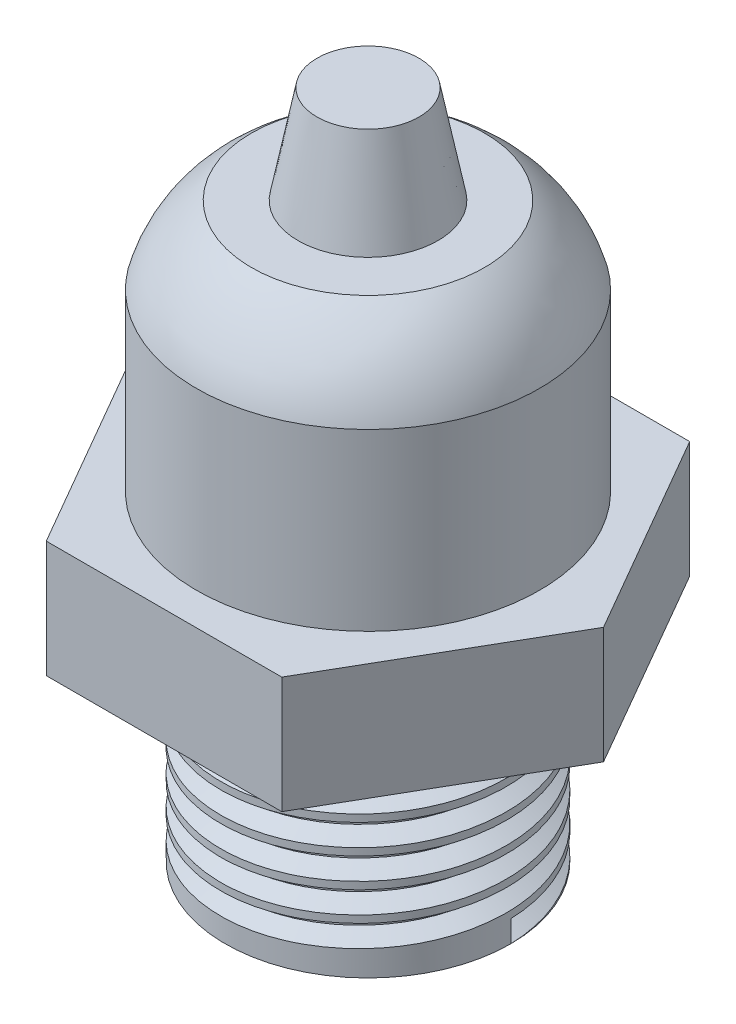
SolidWorks part; units mm, degrees
ref_plane "Front Plane" through (0, 0, 0) normal (0, 0, 1) x (1, 0, 0)
ref_plane "Top Plane" through (0, 0, 0) normal (0, 1, 0) x (1, 0, 0)
ref_plane "Right Plane" through (0, 0, 0) normal (1, 0, 0) x (0, 0, -1)
sketch "Sketch1" plane through (0, 0, 0) normal (0, 1, 0) x (1, 0, 0)
  line L1 (8.0829, 0) -> (4.0415, 7)
  line L2 (4.0415, 7) -> (-4.0415, 7)
  line L3 (-4.0415, 7) -> (-8.0829, 0)
  line L4 (-8.0829, 0) -> (-4.0415, -7)
  line L5 (-4.0415, -7) -> (4.0415, -7)
  line L6 (4.0415, -7) -> (8.0829, 0)
  circle A0 centre (0, 0) radius 7 construction
  dimension "D1" = 14
extrude "Boss-Extrude1" add sketch "Sketch1" along normal blind 4
sketch "Sketch3" plane through (0, 0, 0) normal (0, 0, 1) x (1, 0, 0)
  line L0 (0, 4) -> (0, 16) construction
  line L1 (-4.0415, 4) -> (4.0415, 4) construction
  line L2 (0, 16) -> (1.75, 16)
  line L3 (1.75, 16) -> (2.4, 12.65)
  line L4 (2.4, 12.65) -> (0, 12.65) construction
  line L5 (2.4, 12.65) -> (4, 12.65)
  line L6 (5.8875, 4) -> (5.8875, 10)
  line L7 (4.0415, 4) -> (8.0829, 4) construction
  line L8 (0, 16) -> (0, 4)
  line L9 (0, 4) -> (5.8875, 4)
  arc A0 (4, 12.65) -> (5.8875, 10) centre (1.3088, 8.7359) cw
  dimension "D8" = 4.75
  dimension "D1" = 12
  dimension "D2" = 1.75
  dimension "D3" = 3.35
  dimension "D4" = 2.4
  dimension "D5" = 4
  dimension "D6" = 5.8875
  dimension "D7" = 6
revolve "Revolve1" add sketch "Sketch3" angle 360 about L8 region at (2.6283, 8.9395, 0)
sketch "Sketch4" plane through (0, 0, 0) normal (0, -1, 0) x (1, 0, 0)
  line L0 (3.55, 0) -> (4.9, 0) construction
  circle A0 centre (0, 0) radius 4.9
  circle A1 centre (0, 0) radius 3.55
  point P6 (0, 0)
  dimension "D2" = 9.8
  dimension "D1" = 1.35
extrude "Boss-Extrude3" add sketch "Sketch4" along normal blind 7
thread "Thread1" pitch 1 method cut profile "Thread Profile1" start angle 0, offset 0, length 0, pitch 1, diameter 9.8
ref_plane "Plane1" through (4.9, -7, 0) normal (0, 0, -1) x (-1, 0, 0)
sketch "Thread Profile1" plane through (4.9, -7, 0) normal (0, 0, -1) x (-1, 0, 0)
  line L0 (0, 0) -> (0, 1) construction
  line L1 (0, 0) -> (0.5413, 0.3125)
  line L2 (0.5413, 0.3125) -> (0.5413, 0.4375)
  line L3 (0.5413, 0.4375) -> (0, 0.75)
  line L4 (0.5413, 0.375) -> (0, 0.375) construction
  line L11 (0, 0) -> (0, 0.75)
  point P2 (0, 0)
  dimension "Pitch" = 1
  dimension "Profile_Angle" = 60
  dimension "Profile_Land" = 0.125
  dimension "Profile_Height" = 0.5413
sketch "Sketch8" plane through (0, 0, 0) normal (0, -1, 0) x (1, 0, 0)
  circle A0 centre (0, 0) radius 1
  dimension "D1" = 2
extrude "Boss-Extrude4" add sketch "Sketch8" along normal up to surface (7 mm away) up to face at (0, -7, -4.9)
